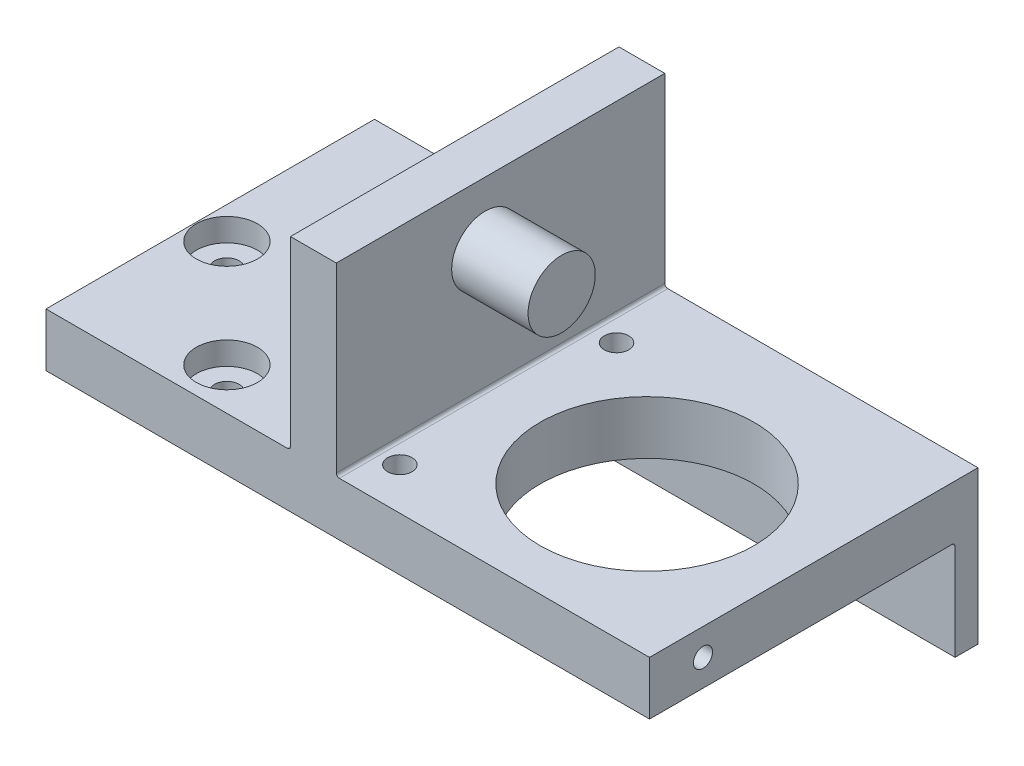
SolidWorks part; units mm, degrees
ref_plane "前视基准面" through (0, 0, 0) normal (0, 0, 1) x (1, 0, 0)
ref_plane "上视基准面" through (0, 0, 0) normal (0, 1, 0) x (1, 0, 0)
ref_plane "右视基准面" through (0, 0, 0) normal (1, 0, 0) x (0, 0, -1)
other "Configuration Table"
sketch "草图1" plane through (0, 0, 0) normal (0, 0, 1) x (1, 0, 0)
  line L1 (-37.104, 2.3263) -> (2.396, 2.3263)
  line L2 (-37.104, 2.3263) -> (-37.104, -1.1737)
  line L3 (-37.104, -1.1737) -> (2.396, -1.1737)
  line L4 (2.396, 2.3263) -> (2.396, -1.1737)
  dimension "D1" = 3.5
  dimension "D2" = 39.5
extrude "凸台-拉伸1" add sketch "草图1" along normal blind 19.5
sketch "草图3" plane through (0, 2.3263, 0) normal (0, 1, 0) x (1, 0, 0)
  line L0 (2.396, -9.75) -> (-13.1566, -9.75) construction
  line L1 (2.396, -19.5) -> (2.396, 0) construction
  circle A0 centre (-7.514, -9.75) radius 7
  dimension "D1" = 9.91
extrude "切除-拉伸1" cut sketch "草图3" against normal up to next
sketch "草图4" plane through (0, -1.1737, 0) normal (0, -1, 0) x (1, 0, 0)
  line L1 (-37.104, 0) -> (2.396, 0)
  line L2 (-37.104, 0) -> (-37.104, -2)
  line L3 (-37.104, -2) -> (2.396, -2)
  line L4 (2.396, 0) -> (2.396, -2)
  dimension "D1" = 2
extrude "凸台-拉伸2" add sketch "草图4" along normal blind 10 from surface starting at face at (-7.514, 2.3263, 16.75)
sketch "草图5" plane through (0, 2.3263, 0) normal (0, 1, 0) x (1, 0, 0)
  line L0 (-37.104, -2.75) -> (2.396, -2.75) construction
  line L1 (-37.104, -19.5) -> (-37.104, 2) construction
  line L2 (2.396, -19.5) -> (2.396, 2) construction
  line L3 (-37.104, -16.75) -> (2.396, -16.75) construction
  line L4 (-37.104, 2) -> (2.396, 2) construction
  line L5 (-37.104, -9.75) -> (2.396, -9.75) construction
  line L6 (-28.014, -2.75) -> (-28.014, -16.75) construction
  line L7 (-16.514, -2.75) -> (-16.514, -23.6041) construction
  circle A0 centre (-35.014, -9.75) radius 0.8
  circle A1 centre (-28.014, -2.75) radius 0.8
  circle A2 centre (-28.014, -16.75) radius 0.8
  circle A3 centre (-16.514, -2.75) radius 0.8
  circle A4 centre (-16.694, -16.75) radius 0.8
  dimension "D3" = 2.09
  dimension "D1" = 4.75
  dimension "D2" = 14
  dimension "D4" = 7
  dimension "D5" = 11.5
  dimension "D6" = 7
extrude "切除-拉伸2" cut sketch "草图5" against normal up to next
sketch "草图6" plane through (-37.104, 0, 0) normal (-1, 0, 0) x (0, 0, 1)
  line L0 (19.5, 2.3263) -> (19.5, -1.1737) construction
  line L1 (19.5, -1.1737) -> (0, -1.1737) construction
  circle A0 centre (16, 0.5763) radius 0.8
  point P0 (16, 0.5763)
  dimension "D1" = 3.5
  dimension "D2" = 1.75
hole_wizard "M1.6 螺纹孔1" positions "草图6" profile "草图7" tap size "M1.6" standard "GB"
sketch "草图7" plane through (-37.104, 0.5763, 16) normal (0, 1, 0) x (0, 0, 1)
  line L0 (0, 0) -> (0, 4.5255)
  line L1 (0, 4.5255) -> (0.625, 4.15)
  line L2 (0.625, 4.15) -> (0.625, 0)
  line L5 (0.625, 0) -> (0, 0)
  line L10 (0, 4.5255) -> (-0.625, 4.15) construction
  line L11 (0, -6.35) -> (0, 107.95) construction
  dimension "螺纹孔钻头直径" = 1.25
  dimension "螺纹孔钻头深度" = 4.15
  dimension "导头角度" = 118
cosmetic thread "孔螺蚊线1" parameters "D1"=2.4, "D2"=1.6
sketch "草图8" plane through (2.396, 0, 0) normal (1, 0, 0) x (0, 0, -1)
  circle A0 centre (-16, 0.5763) radius 0.625 construction
  circle A1 centre (-16, 0.5763) radius 0.625
  point P0 (-16, 0.5763)
hole_wizard "M1.6 螺纹孔2" positions "草图8" profile "草图9" tap size "M1.6" standard "GB"
sketch "草图9" plane through (2.396, 0.5763, 16) normal (0, 1, 0) x (0, 0, -1)
  line L0 (0, 0) -> (0, 4.5255)
  line L1 (0, 4.5255) -> (0.625, 4.15)
  line L2 (0.625, 4.15) -> (0.625, 0)
  line L5 (0.625, 0) -> (0, 0)
  line L10 (0, 4.5255) -> (-0.625, 4.15) construction
  line L11 (0, -6.35) -> (0, 107.95) construction
  dimension "螺纹孔钻头直径" = 1.25
  dimension "螺纹孔钻头深度" = 4.15
  dimension "导头角度" = 118
cosmetic thread "孔螺蚊线2" parameters "D1"=2.4, "D2"=1.6
ref_axis "基准轴1" through (-7.514, -1.1737, 9.75) along (0, 1, 0)
ref_plane "基准面1" through (-7.514, 0, 0) normal (1, 0, 0) x (0, 0, -1)
ref_plane "基准面2" through (0, 0, 9.75) normal (0, 0, 1) x (1, 0, 0)
ref_plane "基准面3" through (-18.104, 0, 0) normal (-1, 0, 0) x (0, 0, 1)
sketch "草图10" plane through (-18.104, 0, 0) normal (-1, 0, 0) x (0, 0, 1)
  line L0 (19.5, 2.3263) -> (-2, 2.3263) construction
  line L1 (-2, 2.3263) -> (19.5, 2.3263)
  line L2 (-2, 2.3263) -> (-2, 14.4296)
  line L3 (-2, 14.4296) -> (19.5, 14.4296)
  line L4 (19.5, 2.3263) -> (19.5, 14.4296)
extrude "凸台-拉伸3" add sketch "草图10" along normal blind 3 contours L4 L3 L2 L1
sketch "草图11" plane through (-18.104, 0, 0) normal (-1, 0, 0) x (0, 0, 1)
  line L0 (-2, 14.4296) -> (19.5, 14.4296) construction
  line L2 (19.5, 2.3263) -> (19.5, 14.4296) construction
  circle A0 centre (9.75, 10.2996) radius 2.2
  dimension "D1" = 4.13
  dimension "D2" = 9.75
  dimension "D3" = 4.4
extrude "凸台-拉伸4" add sketch "草图11" against normal blind 5 contours A0
sketch "草图12" plane through (0, -7.6737, 0) normal (0, -1, 0) x (1, 0, 0)
  line L0 (2.396, -2) -> (2.396, 0) construction
  line L1 (-37.104, 0) -> (2.396, 0)
  line L2 (-37.104, 0) -> (-37.104, -0.5)
  line L3 (-37.104, -0.5) -> (2.396, -0.5)
  line L4 (2.396, 0) -> (2.396, -0.5)
  dimension "D1" = 0.5
extrude "切除-拉伸3" cut sketch "草图12" against normal up to surface (6.5 mm away) up to face at (-35.014, -1.1737, 10.55)
fillet "圆角1" radius 0.2 1 edges at (-17.354, -1.1737, -0.5)
fillet "圆角2" radius 0.2 2 edges at (-21.104, 2.3263, 8.75) (-18.104, 2.3263, 8.75)
sketch "草图13" plane through (0, 2.3263, 0) normal (0, 1, 0) x (1, 0, 0)
  circle A0 centre (-28.014, -2.75) radius 2
  circle A1 centre (-28.014, -16.75) radius 2
  circle A2 centre (-35.014, -9.75) radius 2
extrude "切除-拉伸4" cut sketch "草图13" against normal blind 1.5
